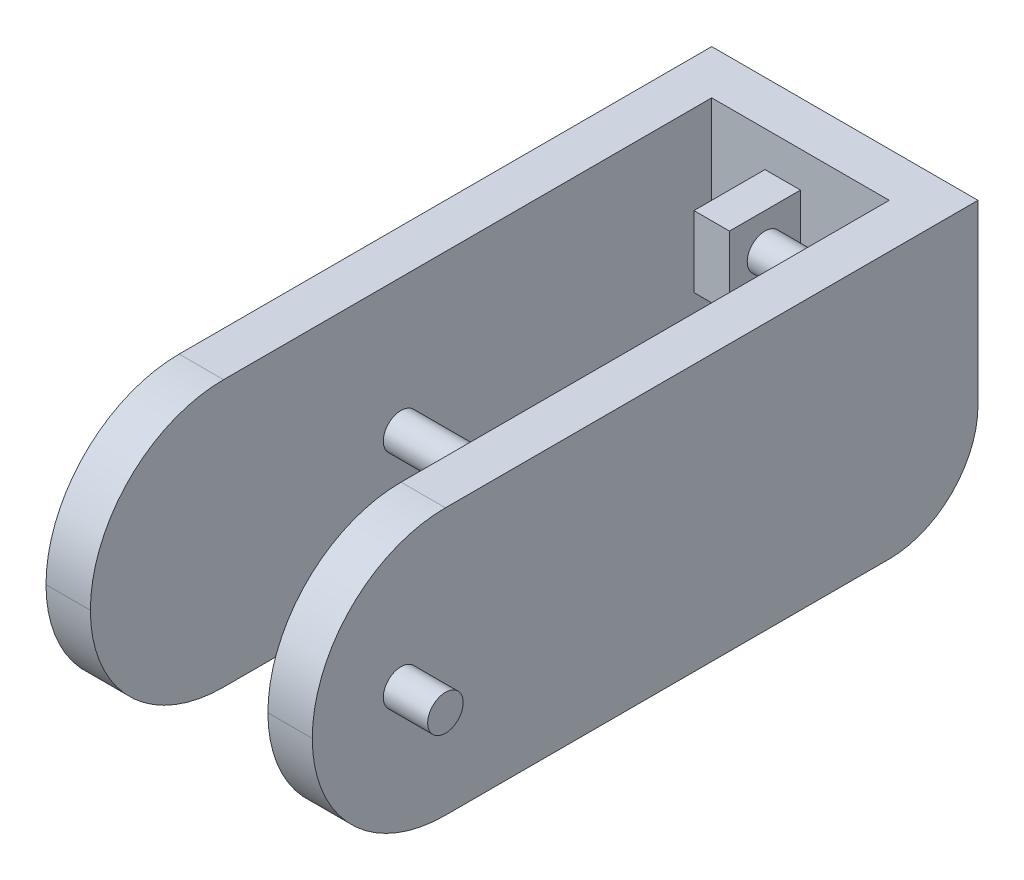
SolidWorks part; units mm, degrees
ref_plane "Front Plane" through (0, 0, 0) normal (0, 0, 1) x (1, 0, 0)
ref_plane "Top Plane" through (0, 0, 0) normal (0, 1, 0) x (1, 0, 0)
ref_plane "Right Plane" through (0, 0, 0) normal (1, 0, 0) x (0, 0, -1)
sketch "Sketch1" plane through (0, 0, 0) normal (0, 1, 0) x (1, 0, 0)
  line L0 (-7.5, -17.5) -> (-7.5, 20)
  line L2 (-5, -17.5) -> (-5, 17.5)
  line L3 (-5, 17.5) -> (5, 17.5)
  line L4 (5, -17.5) -> (5, 17.5)
  line L5 (-5, -17.5) -> (5, 17.5) construction
  line L6 (-5, 17.5) -> (5, -17.5) construction
  line L7 (-7.5, 20) -> (7.5, 20)
  line L8 (7.5, -17.5) -> (7.5, 20)
  line L10 (-5, -17.5) -> (-7.5, -17.5)
  line L11 (5, -17.5) -> (7.5, -17.5)
  line L12 (7.5, -20) -> (7.5, 20) construction
  line L13 (-7.5, -20) -> (7.5, -20) construction
  line L14 (-7.5, -20) -> (-7.5, 20) construction
  line L15 (-5, -17.5) -> (5, -17.5) construction
  point P0 (0, 0)
  dimension "D1" = 10
  dimension "D2" = 35
  dimension "D3" = 2.5
extrude "Boss-Extrude1" add sketch "Sketch1" along normal blind 15
sketch "Sketch4" plane through (5, 0, 0) normal (-1, 0, 0) x (0, 0, 1)
  line L0 (-20, 0) -> (17.5, 0) construction
  line L1 (-20, 15) -> (-20, 0) construction
  circle A0 centre (0, 7.5) radius 1
  dimension "D1" = 2
  dimension "D3" = 20
  dimension "D2" = 7.5
extrude "Boss-Extrude3" add sketch "Sketch4" along normal blind 10
sketch "Sketch5" plane through (7.5, 0, 0) normal (1, 0, 0) x (0, 0, -1)
  line L0 (-17.5, 0) -> (20, 0) construction
  line L1 (-17.5, 15) -> (-17.5, 0) construction
  circle A0 centre (-12.5, 7.5) radius 1
  dimension "D1" = 2
  dimension "D2" = 7.5
  dimension "D3" = 5
extrude "Boss-Extrude4" add sketch "Sketch5" along normal blind 2.5
sketch "Sketch6" plane through (0, 0, -20) normal (0, 0, -1) x (-1, 0, 0)
  line L0 (-7.5, 0) -> (7.5, 0) construction
  line L1 (5, 5) -> (-5, 5)
  line L2 (5, 5) -> (5, 0)
  line L3 (5, 0) -> (-5, 0)
  line L4 (-5, 5) -> (-5, 0)
  line L5 (5, 5) -> (-5, 0) construction
  line L6 (5, 0) -> (-5, 5) construction
  point P0 (0, 2.5)
  dimension "D1" = 10
  dimension "D2" = 5
extrude "Cut-Extrude1" cut sketch "Sketch6" against normal up to next
fillet "Fillet1" radius 7.5 4 edges at (-6.25, 0, 17.5) (-6.25, 15, 17.5) (6.25, 0, 17.5) (6.25, 15, 17.5)
fillet "Fillet2" radius 5 2 edges at (6.25, 0, -20) (-6.25, 0, -20)
sketch "Sketch7" plane through (0, 0, -17.5) normal (0, 0, 1) x (1, 0, 0)
  line L0 (0, -8.25) -> (0, 8.25) construction
  line L1 (0, 9) -> (-2, 9)
  line L3 (0, 13) -> (-2, 13)
  line L4 (-2, 9) -> (-2, 13)
  line L5 (-5, 15) -> (5, 15) construction
  line L8 (0, 9) -> (0, 13)
  point P0 (0, 11)
  dimension "D1" = 4
  dimension "D2" = 4
  dimension "D3" = 2
extrude "Boss-Extrude5" add sketch "Sketch7" along normal blind 4
sketch "Sketch8" plane through (0, 0, 0) normal (1, 0, 0) x (0, 0, -1)
  line L0 (13.5, 13) -> (17.5, 13) construction
  line L1 (13.5, 9) -> (13.5, 13) construction
  circle A0 centre (15.5, 11) radius 1
  dimension "D1" = 2
  dimension "D2" = 2
  dimension "D3" = 2
extrude "Boss-Extrude6" add sketch "Sketch8" along normal blind 2
